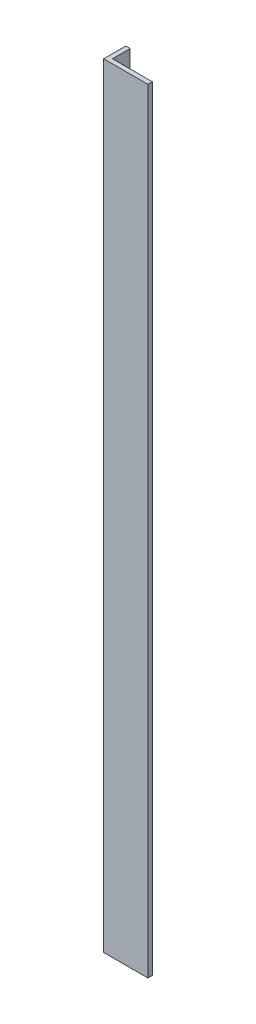
SolidWorks part; units mm, degrees
ref_plane "Front Plane" through (0, 0, 0) normal (0, 0, 1) x (1, 0, 0)
ref_plane "Top Plane" through (0, 0, 0) normal (0, 1, 0) x (1, 0, 0)
ref_plane "Right Plane" through (0, 0, 0) normal (1, 0, 0) x (0, 0, -1)
sketch "Sketch1" plane through (0, 0, 0) normal (0, 1, 0) x (1, 0, 0)
  line L0 (0, 0) -> (0, 10)
  line L1 (0, 10) -> (2, 10)
  line L2 (2, 10) -> (2, 2)
  line L3 (2, 2) -> (20, 2)
  line L4 (20, 2) -> (20, 0)
  line L5 (20, 0) -> (0, 0)
extrude "Boss-Extrude1" add sketch "Sketch1" along normal up to surface (350 mm away)
hole_wizard "Ø3.0 (3) Diameter Hole1" positions "Sketch2" profile "Sketch3" hole size "Ø3.0" standard "ISO" end condition through all
sketch "Sketch2" plane through (2, 128.862, 167.32) normal (1, 0, 0) x (0, -1, 0)
  point P0 (-215.138, 173.32)
  point P1 (-201.138, 173.32)
sketch "Sketch3" plane through (2, 344, -6) normal (0, 1, 0) x (0, 0, -1)
  line L0 (0, 0) -> (0, 2)
  line L1 (0, 2) -> (1.5, 2)
  line L2 (1.5, 2) -> (1.5, 0)
  line L3 (1.5, 0) -> (0, 0)
  line L4 (0, -6.35) -> (0, 107.95) construction
  dimension "Thru Hole Dia." = 3
  dimension "Thru Hole Depth" = 2
hole_wizard "Ø3.0 (3) Diameter Hole2" positions "Sketch4" profile "Sketch5" hole size "Ø3.0" standard "ISO" end condition through all
sketch "Sketch4" plane through (2, 128.862, 167.32) normal (1, 0, 0) x (0, -1, 0)
  point P0 (122.862, 173.32)
  point P1 (108.862, 173.32)
sketch "Sketch5" plane through (2, 6, -6) normal (0, 1, 0) x (0, 0, -1)
  line L0 (0, 0) -> (0, 2)
  line L1 (0, 2) -> (1.5, 2)
  line L2 (1.5, 2) -> (1.5, 0)
  line L3 (1.5, 0) -> (0, 0)
  line L4 (0, -6.35) -> (0, 107.95) construction
  dimension "Thru Hole Dia." = 3
  dimension "Thru Hole Depth" = 2
